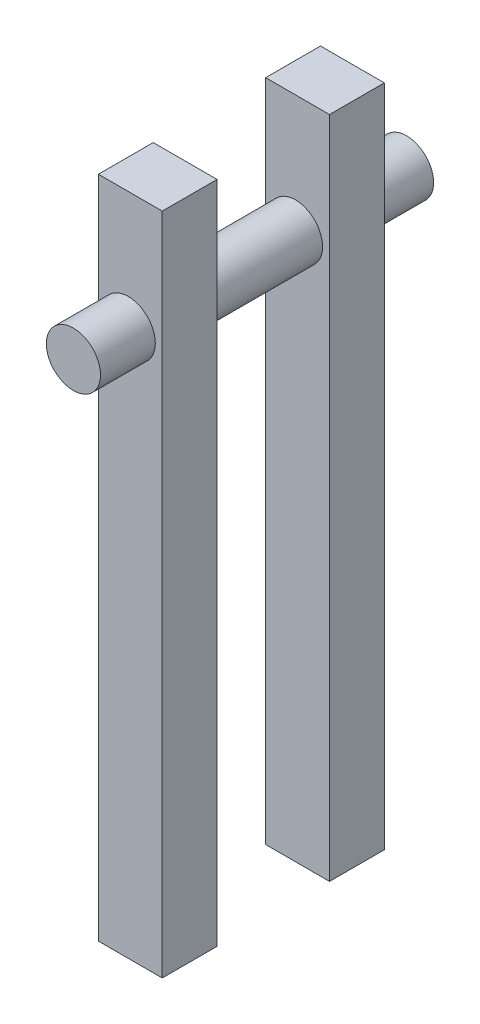
SolidWorks part; units mm, degrees
ref_plane "Front Plane" through (0, 0, 0) normal (0, 0, 1) x (1, 0, 0)
ref_plane "Top Plane" through (0, 0, 0) normal (0, 1, 0) x (1, 0, 0)
ref_plane "Right Plane" through (0, 0, 0) normal (1, 0, 0) x (0, 0, -1)
sketch "Sketch1" plane through (0, 0, 0) normal (1, 0, 0) x (0, 0, -1)
  line L0 (-32.1217, 47.1792) -> (-24.2217, 47.1792)
  line L1 (-8.0217, 47.1792) -> (-0.1217, 47.1792)
  line L2 (-8.0217, 47.1792) -> (-8.0217, -48.5208)
  line L3 (-8.0217, -48.5208) -> (-0.1217, -48.5208)
  line L4 (-0.1217, 47.1792) -> (-0.1217, -48.5208)
  line L5 (-32.1217, 47.1792) -> (-32.1217, -48.5208)
  line L6 (-32.1217, -48.5208) -> (-24.2217, -48.5208)
  line L7 (-24.2217, 47.1792) -> (-24.2217, -48.5208)
  dimension "D1" = 7.9
  dimension "D2" = 95.7
  dimension "D3" = 16.2
extrude "Boss-Extrude1" add sketch "Sketch1" along normal blind 9.2 contours L7 L6 L5 L0
extrude "Boss-Extrude2" add sketch "Sketch1<3>" along normal blind 9.2
sketch "Sketch1<3>" plane through (0, 0, 0) normal (1, 0, 0) x (0, 0, -1) same geometry as "Sketch1"
sketch "Sketch2" plane through (0, 0, 8.0217) normal (0, 0, 1) x (1, 0, 0)
  line L0 (9.2, 47.1792) -> (0, 47.1792) construction
  line L1 (9.2, 47.1792) -> (9.2, -48.5208) construction
  circle A0 centre (4.3, 30.1792) radius 3.9
  dimension "D1" = 7.8
  dimension "D2" = 17
  dimension "D3" = 4.9
extrude "Boss-Extrude3" add sketch "Sketch2" along normal blind 32 and the other way blind 16
